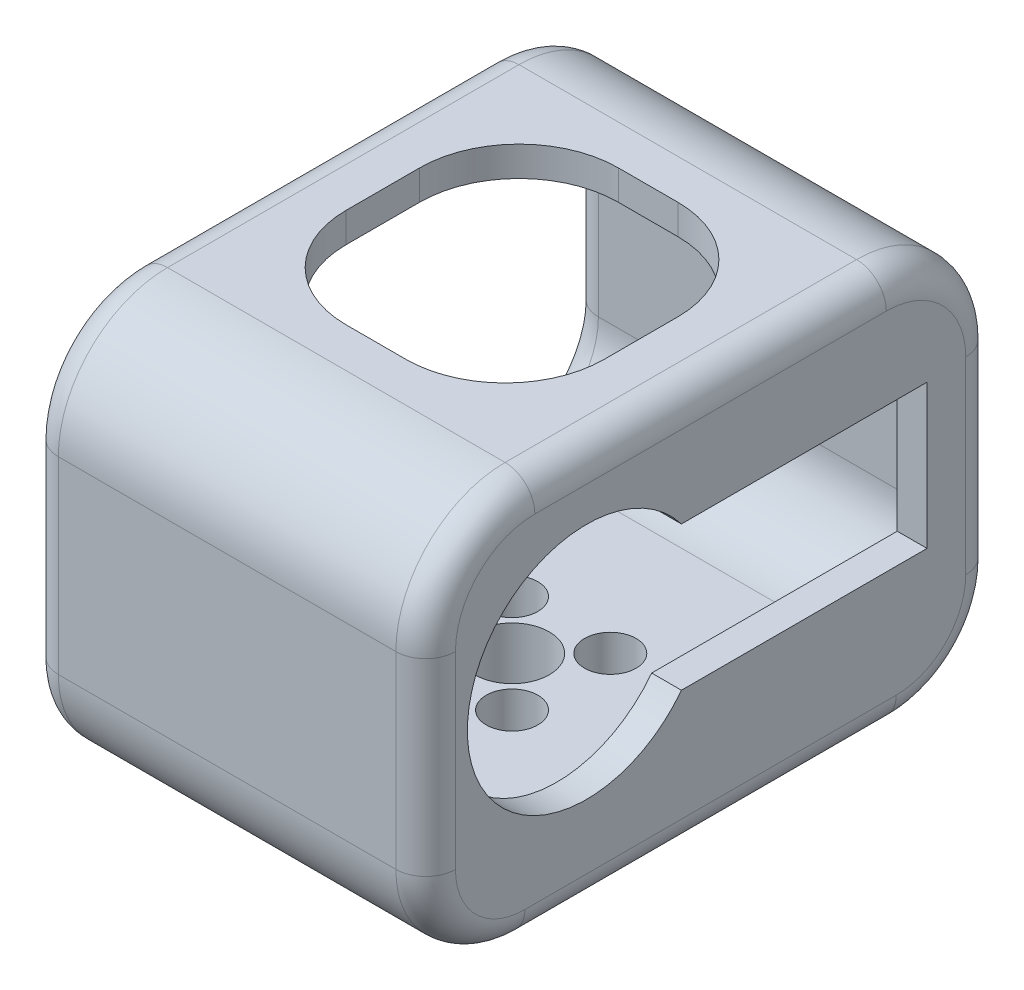
SolidWorks part; units mm, degrees
material "PLA"
ref_plane "Front Plane" through (0, 0, 0) normal (1, 0, 0) x (0, 1, 0)
ref_plane "Top Plane" through (0, 0, 0) normal (0, 0, 1) x (0, 1, 0)
ref_plane "Right Plane" through (0, 0, 0) normal (0, 1, 0) x (-1, 0, 0)
sketch "Sketch1" plane through (0, 0, 0) normal (1, 0, 0) x (0, 0, 1)
  line L0 (-35.2, 0) -> (10.2, 0) construction
  line L1 (-35.2, 12.5) -> (10.2, 12.5)
  line L2 (-35.2, 12.5) -> (-35.2, -12.5)
  line L3 (-35.2, -12.5) -> (10.2, -12.5)
  line L4 (10.2, 12.5) -> (10.2, -12.5)
  line L6 (-34.3002, 7.25) -> (-34.3002, -7.25)
  line L7 (-34.3002, -7.25) -> (-8.6676, -7.25)
  line L8 (-8.6676, 7.25) -> (-34.3002, 7.25)
  line L12 (-12.5, 12.5) -> (-12.5, 25.9141) construction
  line L13 (-12.5, -12.5) -> (-12.5, -25.9141) construction
  line L14 (-38.2, 7.5) -> (-38.2, -7.5)
  line L15 (-30.2, -15.5) -> (5.2, -15.5)
  line L16 (13.2, 7.5) -> (13.2, -7.5)
  line L17 (-30.2, 15.5) -> (5.2, 15.5)
  line L18 (-38.2, 15.5) -> (-38.2, -15.5) construction
  line L19 (-38.2, -15.5) -> (13.2, -15.5) construction
  line L20 (13.2, 15.5) -> (13.2, -15.5) construction
  line L21 (-38.2, 15.5) -> (13.2, 15.5) construction
  line L22 (-30.2, 18.5) -> (5.2, 18.5)
  line L23 (16.2, 7.5) -> (16.2, -7.5)
  line L24 (-30.2, -18.5) -> (5.2, -18.5)
  line L25 (-41.2, 7.5) -> (-41.2, -7.5)
  line L39 (-8.6676, -7.25) -> (-6.8875, -7.25)
  line L40 (-6.8875, 7.25) -> (-8.6676, 7.25)
  arc A2 (-8.6676, 7.25) -> (-8.6676, -7.25) centre (0, 0) ccw
  circle A8 centre (0, 0) radius 12
  arc A13 (-8.6676, 7.25) -> (-8.6676, -7.25) centre (0, 0) ccw
  circle A14 centre (0, 0) radius 10
  arc A15 (-38.2, -7.5) -> (-30.2, -15.5) centre (-30.2, -7.5) ccw
  arc A16 (5.2, -15.5) -> (13.2, -7.5) centre (5.2, -7.5) ccw
  arc A17 (13.2, 7.5) -> (5.2, 15.5) centre (5.2, 7.5) ccw
  arc A18 (-38.2, 7.5) -> (-30.2, 15.5) centre (-30.2, 7.5) cw
  arc A19 (-41.2, 7.5) -> (-30.2, 18.5) centre (-30.2, 7.5) cw
  arc A20 (16.2, 7.5) -> (5.2, 18.5) centre (5.2, 7.5) ccw
  arc A21 (5.2, -18.5) -> (16.2, -7.5) centre (5.2, -7.5) ccw
  arc A22 (-41.2, -7.5) -> (-30.2, -18.5) centre (-30.2, -7.5) ccw
  dimension "D1" = 20
  dimension "D5" = 1.3
  dimension "D6" = 25
  dimension "D8" = 10.2
  dimension "D10" = 8
  dimension "D2" = 25.6326
  dimension "D3" = 25.6326
  dimension "D4" = 14.5
  dimension "D7" = 45.4
  dimension "D9" = 3
  dimension "D11" = 2
  dimension "D12" = 3
extrude "Boss-Extrude1" add sketch "Sketch1" along normal blind 40 contours L1 | L2 | L3 | A8 L7 L6 L8 L4 L1 L2 L3 | L4 A8 | A8 L8 L6 L7 | A14 | A14 L39 L7 A8 L4 L8 L40 | A14 L40 A2 L39 | L4 A8 | L8 A8 L7 A2 | L25 A22 L24 A21 L23 A20 L22 A19 L14 A18 L17 A17 L16 A16 L15 A15 region at (0, -11.9817, -12.5) region at (0, 0, 10.9248) region at (0, 0, 10.1689) region at (0, 0, -22.7509) region at (0, -7.1012, -9.115) region at (0, -7.0984, -7.7776) region at (0, 0, 0) region at (0, -12.7324, -35.4324) region at (0, -17.8171, -12.5)
sketch "Sketch5" plane through (0, 0, 0) normal (0, 0, 1) x (0, 1, 0)
  line L1 (-21.5, 0) -> (0, 0)
  line L2 (-21.5, 0) -> (-21.5, -40)
  line L3 (-21.5, -40) -> (0, -40)
  line L4 (0, 0) -> (0, -40)
  line L5 (-18.5, -40) -> (-18.5, 0) construction
  line L6 (-7.5, -40) -> (7.5, -40) construction
  dimension "D1" = 3
extrude "Boss-Extrude2" add sketch "Sketch5" along normal through all and the other way through all
extrude "Cut-Extrude1" cut sketch "Sketch1<9>" against normal through all both and the other way through all contours A8 L8 L6 L7 | A14 | A14 L39 L7 A8 L4 L8 L40 | A14 L40 A2 L39 | L8 A8 L7 A2 | L4 A8 region at (0, 0, 10.9248) region at (0, 0, 10.1689) region at (0, 0, -22.7509) region at (0, -7.1012, -9.115) region at (0, -7.0984, -7.7776) region at (0, 0, 0)
sketch "Sketch1<9>" plane through (0, 0, 0) normal (1, 0, 0) x (0, 0, 1) same geometry as "Sketch1"
extrude "Cut-Extrude3" cut sketch "Sketch1<10>" along normal offset from surface 3 and the other way through all contours A18 L14 A15 L15 A16 L16 A17 L17 A8 L4 L3 L2 L1 | A8 L7 L6 L8 L4 L1 L2 L3 region at (0, -11.9817, -12.5) region at (0, -12.7324, -35.4324) up to face at (40, 2.2594, -12.5)
sketch "Sketch1<10>" plane through (0, 0, 0) normal (1, 0, 0) x (0, 0, 1) same geometry as "Sketch1"
sketch "Sketch7" plane through (0, -21.5, 0) normal (0, -1, 0) x (1, 0, 0)
  line L0 (20, 16.2) -> (20, -41.2) construction
  line L1 (0, 16.2) -> (40, 16.2) construction
  line L2 (0, -41.2) -> (40, -41.2) construction
  line L3 (15.05, -7.55) -> (24.95, -7.55) construction
  line L4 (40, -12.5) -> (0, -12.5) construction
  line L5 (0, 16.2) -> (0, -41.2) construction
  line L6 (24.95, -7.55) -> (24.95, -17.45) construction
  line L7 (15.05, -7.55) -> (15.05, -17.45) construction
  line L8 (15.05, -17.45) -> (24.95, -17.45) construction
  line L9 (40, 16.2) -> (40, -41.2) construction
  line L10 (15.05, -7.55) -> (24.95, -17.45) construction
  line L11 (15.05, -17.45) -> (24.95, -7.55) construction
  circle A1 centre (20, -12.5) radius 10
  circle A2 centre (15.05, -7.55) radius 1.6
  circle A3 centre (24.95, -7.55) radius 1.6
  circle A4 centre (24.95, -17.45) radius 1.6
  circle A5 centre (15.05, -17.45) radius 1.6
  circle A6 centre (20, -12.5) radius 3.75
  dimension "D1" = 20
  dimension "D2" = 3.2
  dimension "D4" = 7.5
  dimension "D3" = 9.9
extrude "Cut-Extrude4" cut sketch "Sketch7" against normal up to next contours A2 | A3 | A4 | A5 | A6 region at (15.05, -21.5, -7.55) region at (24.95, -21.5, -7.55) region at (24.95, -21.5, -17.45) region at (15.05, -21.5, -17.45) region at (20, -21.5, -12.5)
fillet "Fillet2" radius 10 2 edges at (20, -21.5, -41.2) (20, -21.5, 16.2)
fillet "Fillet3" radius 3 24 edges at (0, 15.2782, -37.9782) (0, 18.5, -12.5) (0, 15.2782, 12.9782) (0, -2, 16.2) (0, -18.5711, 13.2711) (0, -21.5, -12.5) (0, -18.5711, -38.2711) (0, -2, -41.2) (0, 0, 13.2) (0, 13.1569, 10.8569) (0, 15.5, -12.5) (0, 13.1569, -35.8569) (0, 0, -38.2) (0, -13.1569, -35.8569) (0, -15.5, -12.5) (0, -13.1569, 10.8569) (40, -18.5711, 13.2711) (40, -2, 16.2) (40, 15.2782, 12.9782) (40, 18.5, -12.5) (40, 15.2782, -37.9782) (40, -2, -41.2) (40, -18.5711, -38.2711) (40, -21.5, -12.5)
sketch "Sketch8" plane through (0, 18.5, 0) normal (0, 1, 0) x (-1, 0, 0)
  line L0 (-37, 5.2) -> (-37, -30.2) construction
  line L1 (-33, 1.2) -> (-7, 1.2)
  line L2 (-33, 1.2) -> (-33, -26.2)
  line L3 (-33, -26.2) -> (-7, -26.2)
  line L4 (-7, 1.2) -> (-7, -26.2)
  line L5 (-37, 5.2) -> (-3, 5.2) construction
  line L6 (-37, -30.2) -> (-3, -30.2) construction
  line L7 (-3, -30.2) -> (-3, 5.2) construction
  dimension "D1" = 4
  dimension "D2" = 4
  dimension "D3" = 4
  dimension "D4" = 4
extrude "Cut-Extrude5" cut sketch "Sketch8" against normal up to next
fillet "Fillet4" radius 10 4 edges at (33, 17, -26.2) (7, 17, -26.2) (7, 17, 1.2) (33, 17, 1.2)
sketch "Sketch9" plane through (0, -15.5, 0) normal (0, 1, 0) x (-1, 0, 0)
  line L4 (-37, -30.2) -> (-3, -30.2)
  line L5 (-3, -30.2) -> (-3, 5.2)
  line L6 (-3, 5.2) -> (-37, 5.2)
  line L7 (-37, 5.2) -> (-37, -30.2)
  line L8 (-37, -30.2) -> (-3, -30.2)
  line L9 (-3, -30.2) -> (-3, 5.2)
  line L10 (-3, 5.2) -> (-37, 5.2)
  line L11 (-37, 5.2) -> (-37, -30.2)
  circle A10 centre (-24.95, -7.55) radius 2.6
  circle A11 centre (-24.95, -7.55) radius 2.6
  circle A13 centre (-15.05, -7.55) radius 2.6
  circle A14 centre (-15.05, -7.55) radius 2.6
  circle A16 centre (-24.95, -17.45) radius 2.6
  circle A17 centre (-24.95, -17.45) radius 2.6
  circle A19 centre (-15.05, -17.45) radius 2.6
  circle A20 centre (-15.05, -17.45) radius 2.6
  circle M9 centre (-24.95, -7.55) radius 1.6
  circle M12 centre (-15.05, -17.45) radius 1.6
  circle M13 centre (-15.05, -7.55) radius 1.6
  dimension "D1" = 0
  dimension "D2" = 1
  dimension "D3" = 1
  dimension "D4" = 1
  dimension "D5" = 1
extrude "Cut-Extrude6" cut sketch "Sketch9" against normal offset from surface (4 mm away) 2 contours A11 M9 | A14 M13 | A20 M12 | A17 region at (27.4765, -15.5, -7.55) region at (17.5765, -15.5, -7.55) region at (17.5765, -15.5, -17.45) up to face at (24.95, -21.5, -9.15)
